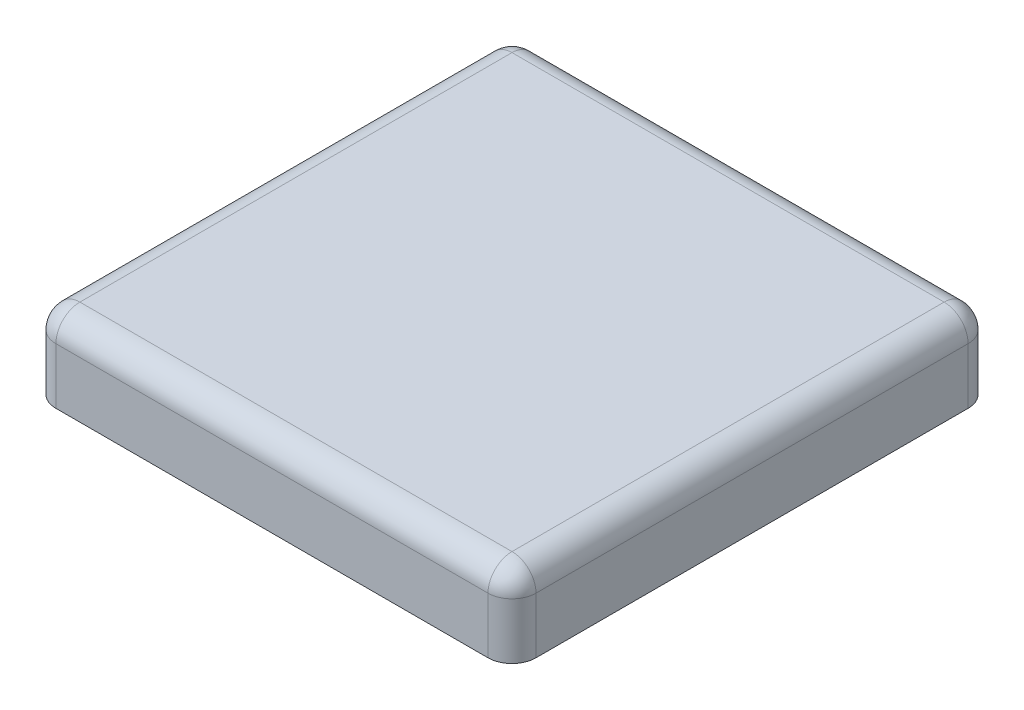
SolidWorks part; units mm, degrees
ref_plane "Front Plane" through (0, 0, 0) normal (0, 0, 1) x (1, 0, 0)
ref_plane "Top Plane" through (0, 0, 0) normal (0, 1, 0) x (1, 0, 0)
ref_plane "Right Plane" through (0, 0, 0) normal (1, 0, 0) x (0, 0, -1)
sketch "Sketch1" plane through (0, 0, 0) normal (0, 1, 0) x (1, 0, 0)
  line L1 (-762, -762) -> (762, -762)
  line L2 (-762, -762) -> (-762, 762)
  line L3 (-762, 762) -> (762, 762)
  line L4 (762, -762) -> (762, 762)
  line L5 (-762, -762) -> (762, 762) construction
  line L6 (-762, 762) -> (762, -762) construction
  point P0 (0, 0)
  dimension "D1" = 1524
  dimension "D2" = 1524
extrude "Boss-Extrude1" add sketch "Sketch1" along normal blind 254
fillet "Fillet1" radius 76.2 8 edges at (0, 254, 762) (-762, 254, 0) (0, 254, -762) (762, 254, 0) (762, 127, -762) (-762, 127, -762) (-762, 127, 762) (762, 127, 762)
shell "Shell1" thickness 76.2 removed face at (0, 0, 0)
scale "Scale1" scale about centroid uniform scaling yes scale factor 0.02
